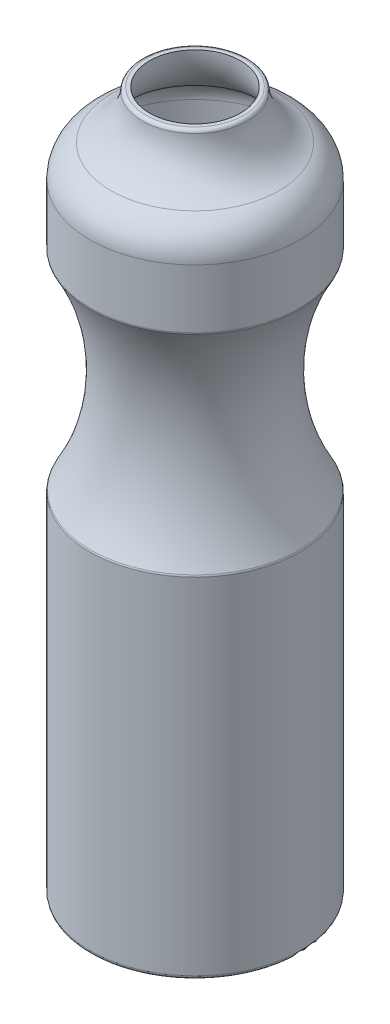
SolidWorks part; units mm, degrees
ref_plane "Front Plane" through (0, 0, 0) normal (0, 0, 1) x (1, 0, 0)
ref_plane "Top Plane" through (0, 0, 0) normal (0, 1, 0) x (1, 0, 0)
ref_plane "Right Plane" through (0, 0, 0) normal (1, 0, 0) x (0, 0, -1)
sketch "Sketch1" plane through (0, 0, 0) normal (1, 0, 0) x (0, 0, -1)
  line L0 (0, 0) -> (0, 200)
  line L1 (0, 0) -> (29, 0)
  line L2 (30, 1) -> (30, 99.7332)
  line L3 (30, 160.2668) -> (30, 177.0871)
  line L4 (14.0313, 200) -> (0, 200)
  circle A0 centre (81.9615, 130) radius 60 construction
  arc A1 (24, 186.2523) -> (15.0293, 199.0625) centre (30, 200) cw
  arc A2 (29.8682, 100.2294) -> (29.8682, 159.7706) centre (81.9615, 130) cw
  arc A3 (30, 177.0871) -> (24, 186.2523) centre (20, 177.0871) ccw
  arc A4 (29, 0) -> (30, 1) centre (29, 1) ccw
  arc A5 (30, 99.7332) -> (29.8682, 100.2294) centre (29, 99.7332) ccw
  arc A6 (15.0293, 199.0625) -> (14.0313, 200) centre (14.0313, 199) ccw
  arc A7 (29.8682, 159.7706) -> (30, 160.2668) centre (29, 160.2668) ccw
  point P10 (0, 0)
  point P11 (20, 199.646)
  point P12 (30, 188.354)
  point P13 (30, 187.1479)
  point P15 (0, 0)
  point P16 (0, 0)
  point P17 (0, 0)
  point P20 (0, 0)
  point P21 (30.3598, 160.6148)
  point P24 (30, 0)
  point P27 (30, 100)
  point P30 (15, 200)
  point P33 (30, 160)
  dimension "D4" = 120
  dimension "D7" = 10
  dimension "D8" = 1
  dimension "D1" = 30
  dimension "D2" = 200
  dimension "D3" = 100
  dimension "D5" = 60
  dimension "D6" = 15
revolve "Revolve1" add sketch "Sketch1" angle 360 about L0 region at (0, 95.0448, -13.9963)
shell "Shell1" thickness 2 removed face at (0, 200, -14.0313)
